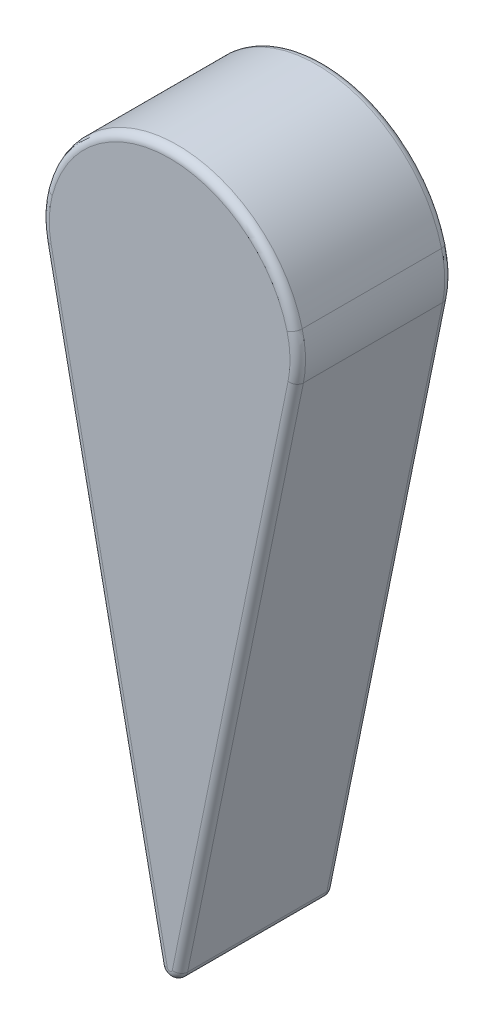
SolidWorks part; units mm, degrees
ref_plane "Front" through (0, 0, 0) normal (0, 0, 1) x (1, 0, 0)
ref_plane "Top" through (0, 0, 0) normal (0, 1, 0) x (1, 0, 0)
ref_plane "Right" through (0, 0, 0) normal (1, 0, 0) x (0, 0, -1)
sketch "Sketch1" plane through (0, 0, 0) normal (0, 0, 1) x (1, 0, 0)
  line L0 (-0.5, 0) -> (0.0007, -2.4496)
  line L1 (0.0007, -2.4496) -> (0.5, 0)
  circle A0 centre (0, 0) radius 0.5
extrude "Boss-Extrude1" add sketch "Sketch1" along normal blind 0.6 contours L1 A0 L0 | A0 L0 L1 region at (0, 0.0003, 0) region at (0.0003, -1.0985, 0)
fillet "Fillet1" radius 0.04 1 edges at (0.0007, -2.4496, 0.3)
fillet "Fillet2" radius 0.4 2 edges at (0.5, 0, 0.3) (-0.5, 0, 0.3)
fillet "Fillet3" radius 0.03 12 edges at (-0.4967, 0.0351, 0) (-0.2637, -1.1564, 0) (0.0006, -2.2896, 0) (0.2643, -1.1563, 0) (0.4967, 0.035, 0) (0.0002, 0.5, 0) (0.0006, -2.2896, 0.6) (-0.2637, -1.1564, 0.6) (-0.4967, 0.0351, 0.6) (0.0002, 0.5, 0.6) (0.4967, 0.035, 0.6) (0.2643, -1.1563, 0.6)
sketch "Sketch2" plane through (0, 0, 0.6) normal (0, 0, 1) x (1, 0, 0)
  line L0 (0.0002, 0.47) -> (0, 0)
  arc A0 (0.4552, 0.117) -> (-0.4551, 0.1173) centre (0, 0) ccw construction
ref_plane "Plane1" through (0, 0, 0) normal (-1, 0.0003, 0) x (0, 0, 1)
